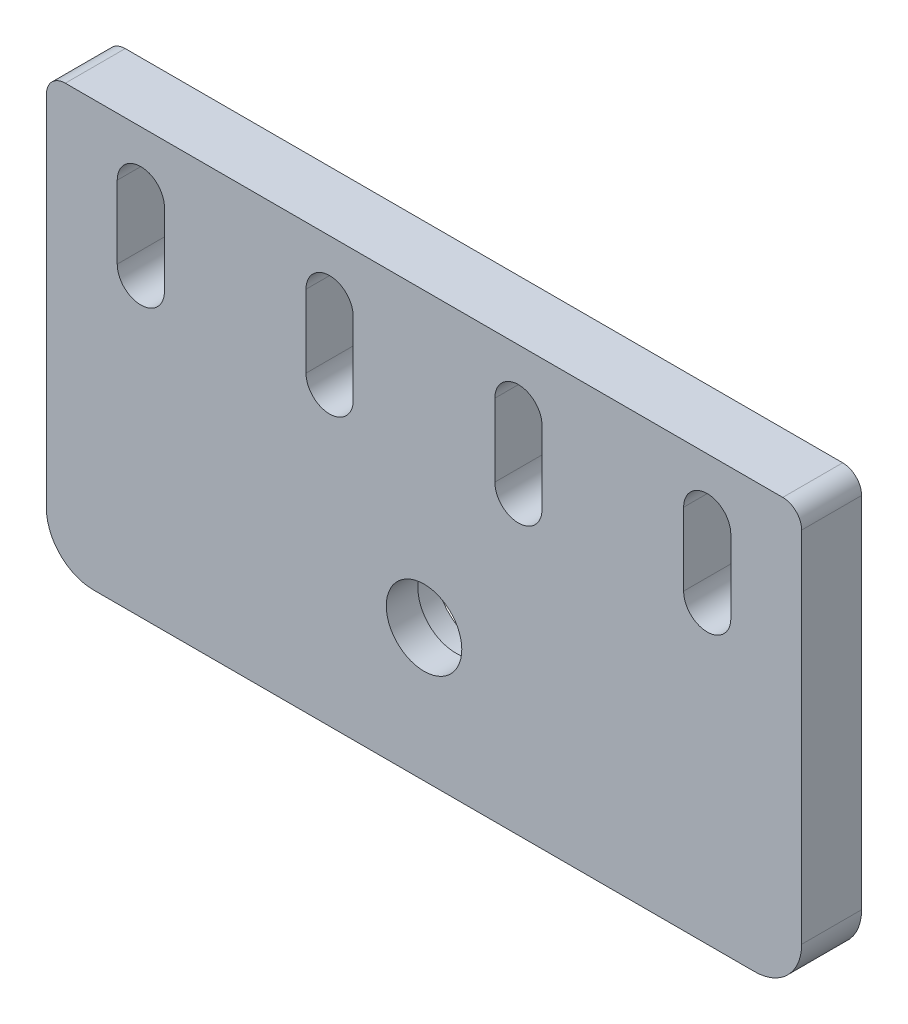
SolidWorks part; units mm, degrees
ref_plane "Front Plane" through (0, 0, 0) normal (0, 0, 1) x (1, 0, 0)
ref_plane "Top Plane" through (0, 0, 0) normal (0, 1, 0) x (1, 0, 0)
ref_plane "Right Plane" through (0, 0, 0) normal (1, 0, 0) x (0, 0, -1)
sketch "Sketch1" plane through (0, 0, 0) normal (0, 0, 1) x (1, 0, 0)
  line L0 (-23.6583, -20.95) -> (-30, -20.95) construction
  line L1 (-28, 10) -> (48, 10)
  line L2 (-30, 8) -> (-30, -30)
  line L4 (50, 8) -> (50, -30)
  line L5 (-5.36, 10) -> (5.36, 10) construction
  line L6 (43.6583, -20.95) -> (50, -20.95) construction
  line L7 (10, -20.95) -> (10, 10) construction
  line L8 (-23.6583, -20.95) -> (10, -20.95) construction
  line L10 (10, -35) -> (10, -20.95) construction
  line L16 (-25, -35) -> (45, -35)
  line L19 (10, -20.95) -> (43.6583, -20.95) construction
  line L20 (-49.855, -30.15) -> (-39.855, -30.15) construction
  circle A0 centre (10, -20.95) radius 4
  arc A1 (50, -30) -> (45, -35) centre (45, -30) cw
  arc A2 (-25, -35) -> (-30, -30) centre (-25, -30) cw
  arc A4 (50, 8) -> (48, 10) centre (48, 8) ccw
  arc A5 (-28, 10) -> (-30, 8) centre (-28, 8) ccw
  point P36 (20.4848, 10)
  point P52 (-30, -30.15)
  dimension "D1" = 8
  dimension "D10" = 6.3417
  dimension "D7" = 2
  dimension "D2" = 5
  dimension "D3" = 30.95
  dimension "D6" = 80
  dimension "D16" = 35
extrude "Boss-Extrude1" add sketch "Sketch1" along normal blind 6.35
hole_wizard "Ø5.0mm Dowel Slot1" positions "Sketch4" profile "Sketch3" size "Ø5.0" standard "ANSI Metric" slot yes
sketch "Sketch4" plane through (0, 0, 6.35) normal (0, 0, 1) x (1, 0, 0)
  line L0 (40, -6.35) -> (40, 6.35) construction
  line L4 (-20, 0) -> (0, 0) construction
  line L5 (0, 0) -> (20, 0) construction
  line L6 (20, 0) -> (40, 0) construction
  line L9 (48, 10) -> (-28, 10) construction
  line L10 (10, -20.95) -> (10, 0) construction
  point P0 (40, 0)
  point P4 (0, 0)
  point P6 (-20, 0)
  point P27 (20, 0)
  dimension "D1" = 12.7
  dimension "D2" = 10
  dimension "D3" = 20
sketch "Sketch3" plane through (40, 0, 6.35) normal (1, 0, 0) x (0, -1, 0)
  line L0 (0, 0) -> (0, 11.5022)
  line L1 (0, 11.5022) -> (2.5, 10)
  line L2 (2.5, 10) -> (2.5, 0)
  line L5 (2.5, 0) -> (0, 0)
  line L10 (0, 11.5022) -> (-2.5, 10) construction
  line L11 (0, -6.35) -> (0, 107.95) construction
  dimension "Hole Dia." = 5
  dimension "Hole Depth" = 10
  dimension "Drill Angle" = 118
sketch "Sketch5" plane through (0, 0, 0) normal (0, 0, -1) x (-1, 0, 0)
  circle A0 centre (-10, -20.95) radius 5.25
  circle A1 centre (-10, -20.95) radius 4 construction
  dimension "D1" = 10.5
extrude "Cut-Extrude1" cut sketch "Sketch5" against normal blind 3
